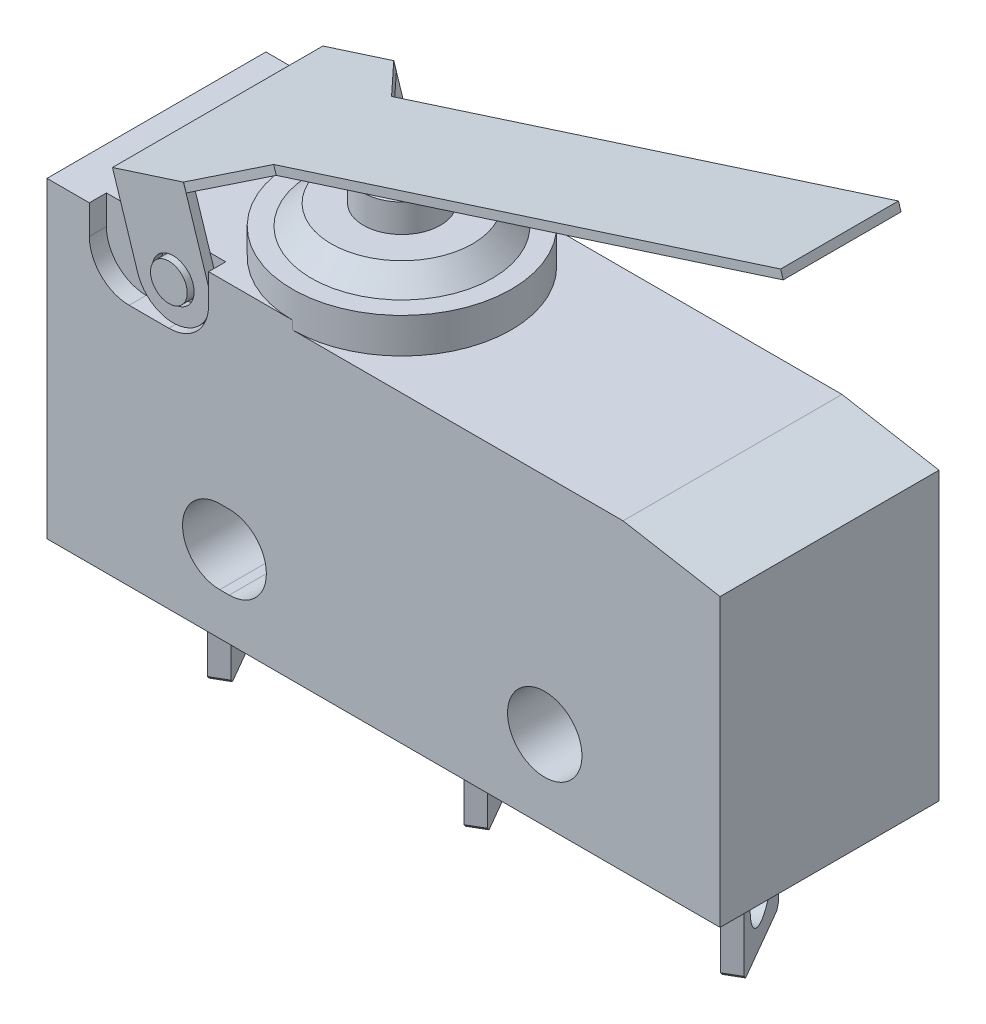
SolidWorks part; units mm, degrees
ref_plane "Front" through (0, 0, 0) normal (0, 0, 1) x (1, 0, 0)
ref_plane "Top" through (0, 0, 0) normal (0, 1, 0) x (1, 0, 0)
ref_plane "Right" through (0, 0, 0) normal (1, 0, 0) x (0, 0, -1)
sketch "Sketch2" plane through (0, 0, 0) normal (0, 0, 1) x (1, 0, 0)
  line L0 (-4.8641, 3.4671) -> (-4.5847, 3.4671)
  line L1 (9.9949, 8.509) -> (7.1139, 9.017)
  line L2 (-9.9949, 9.271) -> (-9.9949, 0)
  line L3 (-9.9949, 0) -> (9.9949, 0)
  line L4 (9.9949, 8.509) -> (9.9949, 0)
  line L5 (-4.8641, 1.2573) -> (-4.5847, 1.2573)
  line L6 (-4.7244, 3.4671) -> (-4.7244, 1.2573) construction
  line L7 (4.7879, 2.3622) -> (-4.5847, 2.3622) construction
  line L8 (7.1139, 9.017) -> (-2.7051, 9.017)
  line L9 (-2.7051, 9.271) -> (-2.7051, 9.017)
  line L12 (-2.7051, 9.271) -> (-9.9949, 9.271)
  line L13 (-2.7051, 9.271) -> (-2.7051, 2.3622) construction
  line L14 (-4.8641, 9.271) -> (-4.8641, 3.4671) construction
  circle A0 centre (4.7879, 2.3622) radius 1.1049
  arc A1 (-4.8641, 3.4671) -> (-4.8641, 1.2573) centre (-4.8641, 2.3622) ccw
  arc A2 (-4.5847, 1.2573) -> (-4.5847, 3.4671) centre (-4.5847, 2.3622) ccw
  point P0 (-4.7244, 2.3622)
  dimension "D4" = 5.207
  dimension "D5" = 2.2098
  dimension "D6" = 2.4892
  dimension "D7" = 6.6548
  dimension "D9" = 7.493
  dimension "D13" = 6.9088
  dimension "D1" = 19.9898
  dimension "D2" = 2.3622
  dimension "D3" = 9.5123
  dimension "D10" = 0.508
  dimension "D11" = 10
extrude "Extrude1" add sketch "Sketch2" along normal mid plane 6.5024
sketch "Sketch11" plane through (0.218, -2.527, 0) normal (0, 0, 1) x (1, 0, 0)
  line L0 (-6.1731, 11.544) -> (-6.1731, 12.5892)
  line L1 (-6.1731, 12.5892) -> (-5.6112, 12.5892)
  line L2 (-5.6112, 12.5892) -> (-5.0204, 13.18)
  line L3 (-5.0204, 13.18) -> (-4.0661, 13.18)
  line L4 (-4.0661, 13.18) -> (-4.0661, 14.0155)
  line L5 (-2.9231, 11.798) -> (-2.9231, 4.8892) construction
  line L6 (-2.9231, 14.2872) -> (-2.9231, 11.544)
  line L7 (-2.9231, 11.544) -> (-6.1731, 11.544)
  line L8 (6.8959, 11.544) -> (-2.9231, 11.544) construction
  line L9 (-2.9231, 14.2872) -> (-2.9231, 15.1227) construction
  arc A0 (-4.0661, 14.0155) -> (-2.9231, 14.2872) centre (-2.9231, 11.7472) cw
  circle A1 centre (4.5699, 4.8892) radius 1.1049 construction
  dimension "D2" = 9.398
  dimension "D6" = 2.54
  dimension "D1" = 7.7
  dimension "D3" = 2.286
  dimension "D4" = 6.5
  dimension "D5" = 135
revolve "Revolve1" add sketch "Sketch11" angle 360 about L9
sketch "Sketch5" plane through (0, 0, 3.2512) normal (0, 0, 1) x (1, 0, 0)
  line L0 (-8.7376, 9.271) -> (-8.7376, 8.4074)
  line L1 (-7.5565, 7.2263) -> (-6.3754, 7.2263)
  line L2 (-5.1943, 8.4074) -> (-5.1943, 9.271)
  line L3 (-2.7051, 9.271) -> (-9.9949, 9.271) construction
  line L6 (-5.1943, 9.271) -> (-8.7376, 9.271)
  line L7 (-2.7051, 9.271) -> (-2.7051, 2.3622) construction
  circle A1 centre (-7.5565, 8.4074) radius 0.5461 construction
  arc A2 (-8.7376, 8.4074) -> (-7.5565, 7.2263) centre (-7.5565, 8.4074) ccw
  arc A3 (-6.3754, 7.2263) -> (-5.1943, 8.4074) centre (-6.3754, 8.4074) ccw
  circle A5 centre (-6.3754, 8.4074) radius 0.5461
  dimension "D4" = 0.635
  dimension "D5" = 1.0922
  dimension "D6" = 0.635
  dimension "D1" = 6.0452
  dimension "D2" = 4.8514
  dimension "D3" = 0.635
extrude "Cut-Extrude2" cut sketch "Sketch5" against normal blind 0.508
mirror "Mirror1" about plane through (0, 0, 0) normal (0, 0, 1) of "Cut-Extrude2"
ref_plane "Plane1" through (-7.62, 0, 0) normal (1, 0, 0) x (0, 0, -1)
ref_axis "Axis1" through (-7.62, -4.177, 0) along (0, 1, 0)
ref_plane "Plane2" through (-5.715, 0, 3.2996) normal (0.866, 0, -0.5) x (-0.5, 0, -0.866)
sketch "Sketch10" plane through (-7.5882, 0, 0.055) normal (0.866, 0, -0.5) x (-0.5, 0, -0.866)
  line L0 (-1.3335, 0) -> (-1.3335, -3.0734)
  line L1 (-1.2065, -3.2004) -> (1.3335, -3.2004)
  line L2 (1.4605, -3.0734) -> (1.4605, 0)
  line L3 (1.4605, 0) -> (-1.3335, 0)
  line L4 (0.0635, -3.2004) -> (0.0635, -1.7018) construction
  line L5 (0.0635, 0) -> (0.0635, -1.7018) construction
  line L6 (-1.3335, -3.0734) -> (-1.2065, -3.2004)
  line L7 (1.3335, -3.2004) -> (1.4605, -3.0734)
  line L8 (0.0635, -4.177) -> (0.0635, 17.3088) construction
  circle A0 centre (0.0635, -1.7018) radius 0.9017
  point P1 (-1.3335, -3.2004)
  point P3 (1.4605, -3.2004)
  dimension "D2" = 1.8034
  dimension "D1" = 3.2004
  dimension "D3" = 2.794
  dimension "D4" = 1.4986
  dimension "D5" = 0.127
  dimension "D6" = 45
  dimension "D7" = 0.127
  dimension "D8" = 45
extrude "Extrude6" add sketch "Sketch10" along normal mid plane 0.508
pattern_linear "LPattern1" count 3 spacing 7.62 along (1, 0, 0) of "Extrude6"
sketch "Sketch6" plane through (0, 0, 0) normal (0, 0, 1) x (1, 0, 0)
  line L0 (-8.0998, 10.1543) -> (10.3697, 16.0904)
  line L1 (10.3697, 16.0904) -> (10.292, 16.3322)
  line L2 (10.292, 16.3322) -> (-8.1776, 10.3961)
  line L3 (-8.1776, 10.3961) -> (-8.0998, 10.1543)
  line L4 (-5.1943, 8.4074) -> (-5.1943, 9.271) construction
  line L10 (-8.0998, 10.1543) -> (-7.4295, 8.0686) construction
  line L11 (-5.3213, 8.7462) -> (-5.9916, 10.8319) construction
  circle A0 centre (4.7879, 2.3622) radius 1.1049 construction
  circle A1 centre (-6.3754, 8.4074) radius 0.5461 construction
  arc A2 (-2.7051, 11.7602) -> (-3.8481, 11.4885) centre (-2.7051, 9.2202) ccw construction
  arc A6 (-7.4295, 8.0686) -> (-5.3213, 8.7462) centre (-6.3754, 8.4074) ccw construction
  dimension "D1" = 5.5041
  dimension "D2" = 13.97
  dimension "D3" = 0.127
  dimension "D4" = 19.4
  dimension "D5" = 0.254
extrude "Extrude3" add sketch "Sketch6" along normal mid plane 3.5 separate body
sketch "Sketch8" plane through (0, 0, 3.2512) normal (0, 0, 1) x (1, 0, 0)
  line L0 (-5.3213, 8.7462) -> (-5.9916, 10.8319) construction
  line L1 (-8.0998, 10.1543) -> (-7.4295, 8.0686) construction
  line L2 (-5.3213, 8.7462) -> (-6.0694, 11.0737)
  line L3 (-8.1776, 10.3961) -> (-7.4295, 8.0686)
  line L4 (10.292, 16.3322) -> (-8.1776, 10.3961) construction
  line L5 (-6.0694, 11.0737) -> (-8.1776, 10.3961)
  arc A1 (-7.4295, 8.0686) -> (-5.3213, 8.7462) centre (-6.3754, 8.4074) ccw construction
  arc A3 (-7.4295, 8.0686) -> (-5.3213, 8.7462) centre (-6.3754, 8.4074) ccw
  circle A4 centre (-6.3754, 8.4074) radius 0.6223
  circle A6 centre (-6.3754, 8.4074) radius 0.6223
  dimension "D1" = 0.0762
extrude "Extrude4" add sketch "Sketch8" against normal blind 0.254 from offset 0.127 separate body offset against normal yes
sketch "Sketch9" plane through (0, 0, 1.75) normal (0, 0, 1) x (1, 0, 0)
  line L0 (-5.3213, 8.7462) -> (-5.9916, 10.8319) construction
  line L1 (-8.1776, 10.3961) -> (-8.0998, 10.1543) construction
  line L2 (-8.0998, 10.1543) -> (10.3697, 16.0904) construction
  line L3 (10.292, 16.3322) -> (-8.1776, 10.3961) construction
  line L4 (-5.9916, 10.8319) -> (-6.0694, 11.0737)
  line L5 (-8.1776, 10.3961) -> (-8.0998, 10.1543)
  line L6 (-8.0998, 10.1543) -> (-5.9916, 10.8319)
  line L7 (-6.0694, 11.0737) -> (-8.1776, 10.3961)
extrude "Extrude5" add sketch "Sketch9" along normal up to surface (1.1202 mm away) up to face at (-5.7531, 8.4074, 2.8702)
mirror "Mirror7" about plane through (0, 0, 0) normal (0, 0, 1) of bodies 116
combine bodies "Combine1" operation type add bodies to combine 118 114 116
chamfer "Chamfer1" distance 1.3716 angle 45 2 edges
sketch "Sketch12" plane through (0, 0, 0) normal (0, 0, 1) x (1, 0, 0)
  line L0 (-6.3754, 8.4074) -> (-7.1235, 10.7349) construction
  line L1 (-6.0694, 11.0737) -> (-8.1776, 10.3961) construction
  line L2 (-7.1235, 10.7349) -> (10.292, 16.3322) construction
  line L3 (-6.3754, 8.4074) -> (-6.4397, 10.8513) construction
  line L4 (-6.4397, 10.8513) -> (11.8468, 11.3322) construction
  line L5 (-6.3754, 8.4074) -> (-6.5338, 10.847) construction
  line L6 (-6.5338, 10.847) -> (11.7206, 12.0322) construction
  line L7 (-6.3754, 8.4074) -> (-6.2396, 10.8484) construction
  line L8 (-6.2396, 10.8484) -> (12.025, 9.8322) construction
  arc A0 (12.025, 9.8322) -> (10.292, 16.3322) centre (-6.3754, 8.4074) ccw construction
  point P14 (11.7206, 12.0322)
  point P15 (11.8468, 11.3322)
  point P16 (12.025, 9.8322)
  dimension "D1" = 5
  dimension "D2" = 0.7
  dimension "D3" = 1.5
equation "\"D4@Sketch6\" = 19.4/25.4"
